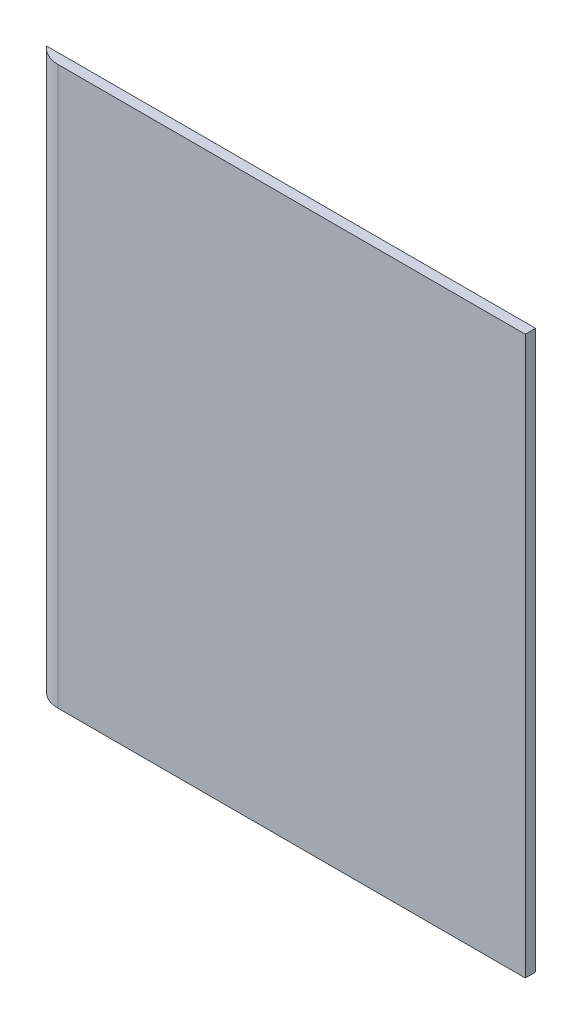
SolidWorks part; units mm, degrees
ref_plane "Front Plane" through (0, 0, 0) normal (0, 0, 1) x (1, 0, 0)
ref_plane "Top Plane" through (0, 0, 0) normal (0, 1, 0) x (1, 0, 0)
ref_plane "Right Plane" through (0, 0, 0) normal (1, 0, 0) x (0, 0, -1)
sketch "Sketch3" plane through (0, 0, 0) normal (0, 0, 1) x (1, 0, 0)
  line L1 (0, 0) -> (175.4, 0)
  line L2 (0, 0) -> (0, 200)
  line L3 (0, 200) -> (175.4, 200)
  line L4 (175.4, 0) -> (175.4, 200)
  dimension "D1" = 175.4
  dimension "D2" = 200
extrude "Boss-Extrude1" add sketch "Sketch3" along normal blind 3.7
fillet "Fillet1" radius 10 1 edges at (0, 100, 3.7)
